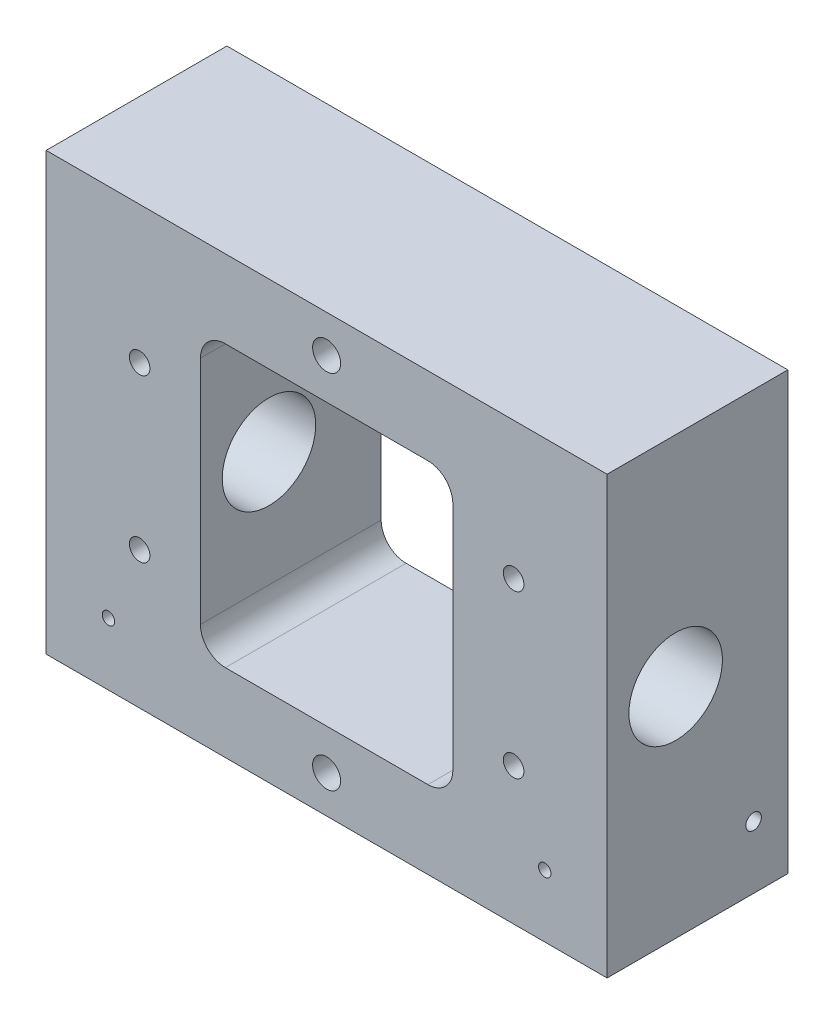
SolidWorks part; units mm, degrees
material "Lega 6061"
ref_plane "Piano frontale" through (0, 0, 0) normal (0, 0, 1) x (1, 0, 0)
ref_plane "Piano superiore" through (0, 0, 0) normal (0, 1, 0) x (1, 0, 0)
ref_plane "Piano destro" through (0, 0, 0) normal (1, 0, 0) x (0, 0, -1)
sketch "Schizzo1" plane through (0, 0, 0) normal (0, 0, 1) x (1, 0, 0)
  line L1 (0, 0) -> (90, 0)
  line L2 (0, 0) -> (0, 70)
  line L3 (0, 70) -> (90, 70)
  line L4 (90, 0) -> (90, 70)
  dimension "D1" = 90
  dimension "D2" = 70
extrude "Estrusione-Estrusione1" add sketch "Schizzo1" against normal blind 29
sketch "Schizzo2" plane through (0, 0, 0) normal (-1, 0, 0) x (0, 0, 1)
  line L0 (-29, 35) -> (0, 35) construction
  line L1 (-29, 70) -> (-29, 0) construction
  line L2 (0, 70) -> (0, 0) construction
  circle A0 centre (-11, 35) radius 7.5
  dimension "D1" = 15
  dimension "D2" = 18
extrude "Taglio-Estrusione1" cut sketch "Schizzo2" against normal through all
sketch "Schizzo3" plane through (0, 0, -29) normal (0, 0, -1) x (-1, 0, 0)
  line L0 (-94.314, 64) -> (4.9562, 64) construction
  line L2 (-90, 70) -> (0, 70) construction
  line L4 (-90, 35) -> (0, 35) construction
  line L5 (-90, 0) -> (-90, 70) construction
  line L6 (0, 70) -> (0, 0) construction
  line L7 (-94.314, 6) -> (4.9562, 6) construction
  line L8 (-45, 70) -> (-45, 0) construction
  line L9 (0, 0) -> (-90, 0) construction
  point P16 (-45, 64)
  point P17 (-45, 6)
  dimension "D1" = 6
hole_wizard "Foro lamato per Vite M4 a testa cilindrica piana-1" positions "Schizzo3D1" profile "Schizzo4" counterbore size "M4" standard "ISO" end condition through all
sketch3d "Schizzo3D1"
  point P0 (45, 64, -29)
  point P3 (45, 6, -29)
sketch "Schizzo4" plane through (45, 64, -29) normal (1, 0, 0) x (0, 1, 0)
  line L0 (0, 0) -> (0, 29)
  line L1 (0, 29) -> (2.25, 29)
  line L3 (2.25, 29) -> (2.25, 2.6)
  line L4 (2.25, 2.6) -> (4, 2.6)
  line L5 (4, 2.6) -> (4, 0)
  line L7 (4, 0) -> (0, 0)
  line L11 (0, -6.35) -> (0, 107.95) construction
  dimension "Thru Hole Dia." = 4.5
  dimension "Thru Hole Depth" = 29
  dimension "C'Bore Dia." = 8
  dimension "C'Bore Depth" = 2.6
ref_axis "Assi1" through (90, 35, -11) along (-1, 0, 0)
sketch "Schizzo14" plane through (0, 0, 0) normal (0, 0, 1) x (1, 0, 0)
  line L0 (45, 70) -> (45, 0) construction
  line L2 (61.25, 12.5) -> (28.75, 12.5)
  line L3 (65.25, 16.5) -> (65.25, 53.5)
  line L4 (90, 35) -> (0, 35) construction
  line L5 (61.25, 57.5) -> (28.75, 57.5)
  line L6 (24.75, 16.5) -> (24.75, 53.5)
  line L7 (65.25, 12.5) -> (24.75, 57.5) construction
  line L8 (65.25, 57.5) -> (24.75, 12.5) construction
  line L9 (0, 0) -> (90, 0) construction
  arc A0 (61.25, 57.5) -> (65.25, 53.5) centre (61.25, 53.5) cw
  arc A1 (65.25, 16.5) -> (61.25, 12.5) centre (61.25, 16.5) cw
  arc A2 (28.75, 12.5) -> (24.75, 16.5) centre (28.75, 16.5) cw
  arc A3 (24.75, 53.5) -> (28.75, 57.5) centre (28.75, 53.5) cw
  point P2 (45, 35)
  point P3 (45, 35)
  dimension "D1" = 4
  dimension "D2" = 45
  dimension "D3" = 40.5
  dimension "D4" = 12.5
extrude "Taglio-Estrusione4" cut sketch "Schizzo14" against normal through all
sketch "Schizzo16" plane through (0, 0, 0) normal (0, 0, 1) x (1, 0, 0)
  line L0 (45, 70) -> (45, 0) construction
  line L1 (0, 35) -> (90, 35) construction
  line L2 (0, 70) -> (0, 0) construction
  line L3 (0, 0) -> (90, 0) construction
  circle A0 centre (10, 10) radius 1
  circle A1 centre (80, 10) radius 1
  dimension "D1" = 2
  dimension "D2" = 10
  dimension "D3" = 10
  dimension "D4" = 35
  dimension "D5" = 25
extrude "Taglio-Estrusione6" cut sketch "Schizzo16" against normal through all
sketch "Schizzo17" plane through (0, 0, -29) normal (0, 0, -1) x (-1, 0, 0)
  line L0 (-45, 70) -> (-45, 0.5122) construction
  line L1 (-90, 70) -> (0, 70) construction
  line L2 (-45, 70) -> (-45, 0) construction
  line L3 (0, 35) -> (-90, 35) construction
  circle A0 centre (-10, 10) radius 8
  circle A1 centre (-80, 10) radius 8
  dimension "D1" = 16
extrude "Taglio-Estrusione8" cut sketch "Schizzo17" against normal blind 13
sketch "Schizzo18" plane through (0, 0, 0) normal (0, 0, 1) x (1, 0, 0)
  line L0 (0, 70) -> (90, 0) construction
  line L1 (90, 70) -> (0, 0) construction
  line L2 (45, 35) -> (45, 70) construction
  line L3 (15, 35.0996) -> (15, 74.2174) construction
  line L4 (24.75, 35) -> (0, 35) construction
  line L5 (24.75, 53.5) -> (24.75, 16.5) construction
  line L6 (90, 35) -> (0, 35) construction
  line L7 (90, 70) -> (0, 70) construction
  line L8 (45, 70) -> (45, 0) construction
  point P9 (15, 22)
  point P11 (45, 35)
  point P17 (15, 48)
  point P24 (75, 22)
  point P25 (75, 48)
  dimension "D1" = 13
  dimension "D2" = 30
hole_wizard "Foro filettato M4-1" positions "Schizzo20" profile "Schizzo19" tap size "M4" standard "ISO" end condition through all
sketch "Schizzo20" plane through (0, 0, 0) normal (0, 0, 1) x (1, 0, 0)
  point P0 (15, 48)
  point P3 (15, 22)
  point P6 (75, 48)
  point P9 (75, 22)
cosmetic thread "Filettatura del foro1" parameters "D2"=4
cosmetic thread "Filettatura del foro2" parameters "D2"=4
cosmetic thread "Filettatura del foro3" parameters "D2"=4
cosmetic thread "Filettatura del foro4" parameters "D2"=4
sketch "Schizzo19" plane through (15, 48, 0) normal (1, 0, 0) x (0, -1, 0)
  line L0 (0, 0) -> (0, 29)
  line L1 (0, 29) -> (1.65, 29)
  line L2 (1.65, 29) -> (1.65, 0)
  line L5 (1.65, 0) -> (0, 0)
  line L11 (0, -6.35) -> (0, 107.95) construction
  dimension "Thru Tap Drill Dia." = 3.3
  dimension "Thru Tap Drill Depth" = 29
sketch "Schizzo21" plane through (0, 0, -29) normal (0, 0, -1) x (-1, 0, 0)
  line L0 (-70, 73.919) -> (-70, -6.106) construction
  line L1 (-45, 70) -> (-45, 0) construction
  line L2 (-90, 70) -> (0, 0) construction
  line L3 (0, 70) -> (-90, 0) construction
  line L5 (-20, 72.5272) -> (-20, -6.106) construction
  point P6 (-70, 54.4444)
  point P9 (-70, 15.5556)
  point P14 (-20, 54.4444)
  point P15 (-20, 15.5556)
  dimension "D1" = 25
  dimension "D2" = 25
hole_wizard "Foro filettato M3-1" positions "Schizzo23" profile "Schizzo22" tap size "M3" standard "ISO"
sketch "Schizzo23" plane through (0, 0, -29) normal (0, 0, -1) x (-1, 0, 0)
  point P0 (-70, 54.4444)
  point P3 (-70, 15.5556)
  point P6 (-20, 54.4444)
  point P9 (-20, 15.5556)
sketch "Schizzo22" plane through (70, 54.4444, -29) normal (1, 0, 0) x (0, 1, 0)
  line L0 (0, 0) -> (0, 12.7511)
  line L1 (0, 12.7511) -> (1.25, 12)
  line L2 (1.25, 12) -> (1.25, 0)
  line L5 (1.25, 0) -> (0, 0)
  line L10 (0, 12.7511) -> (-1.25, 12) construction
  line L11 (0, -6.35) -> (0, 107.95) construction
  dimension "Tap Drill Dia." = 2.5
  dimension "Tap Drill Depth" = 12
  dimension "Drill Angle" = 118
cosmetic thread "Filettatura del foro5" parameters "D1"=8, "D2"=3
cosmetic thread "Filettatura del foro6" parameters "D1"=8, "D2"=3
cosmetic thread "Filettatura del foro7" parameters "D1"=8, "D2"=3
cosmetic thread "Filettatura del foro8" parameters "D1"=8, "D2"=3
sketch "Schizzo24" plane through (0, 0, 0) normal (-1, 0, 0) x (0, 0, 1)
  line L0 (-16, 18) -> (-16, 2) construction
  line L1 (-16, 10) -> (-29, 10) construction
  point P6 (-23.5, 10)
  dimension "D1" = 7.5
hole_wizard "Foro filettato M3-2" positions "Schizzo26" profile "Schizzo27" tap size "M3" standard "ISO" end condition up to next
sketch "Schizzo26" plane through (0, 0, 0) normal (-1, 0, 0) x (0, 0, 1)
  point P0 (-23.5, 10)
sketch "Schizzo27" plane through (0, 10, -23.5) normal (0, 1, 0) x (0, 0, 1)
  line L0 (0, 0) -> (0, 2)
  line L1 (0, 2) -> (1.25, 2)
  line L2 (1.25, 2) -> (1.25, 0)
  line L5 (1.25, 0) -> (0, 0)
  line L11 (0, -6.35) -> (0, 107.95) construction
  dimension "Thru Tap Drill Dia." = 2.5
  dimension "Thru Tap Drill Depth" = 2
cosmetic thread "Filettatura del foro9" parameters "D2"=3
sketch "Schizzo28" plane through (0, 0, 0) normal (0, -1, 0) x (1, 0, 0)
  line L0 (2, -16) -> (18, -16) construction
  line L1 (10, -16) -> (10, -29) construction
  line L2 (94.314, -29) -> (-4.9562, -29) construction
  point P8 (10, -23.5)
  dimension "D1" = 7.5
hole_wizard "Foro filettato M3-3" positions "Schizzo30" profile "Schizzo31" tap size "M3" standard "ISO" end condition up to next
sketch "Schizzo30" plane through (0, 0, 0) normal (0, -1, 0) x (-1, 0, 0)
  point P0 (-10, 23.5)
sketch "Schizzo31" plane through (10, 0, -23.5) normal (1, 0, 0) x (0, 0, -1)
  line L0 (0, 0) -> (0, 2)
  line L1 (0, 2) -> (1.25, 2)
  line L2 (1.25, 2) -> (1.25, 0)
  line L5 (1.25, 0) -> (0, 0)
  line L11 (0, -6.35) -> (0, 107.95) construction
  dimension "Thru Tap Drill Dia." = 2.5
  dimension "Thru Tap Drill Depth" = 2
cosmetic thread "Filettatura del foro10" parameters "D2"=3
sketch "Schizzo32" plane through (0, 0, 0) normal (0, -1, 0) x (1, 0, 0)
  line L0 (72, -16) -> (88, -16) construction
  line L1 (72, -16) -> (88, -16) construction
  line L2 (80, -16) -> (80, -29) construction
  line L3 (94.314, -29) -> (-4.9562, -29) construction
  line L5 (90, -29) -> (90, 0) construction
  point P9 (80, -23.5)
  point P12 (90, -20.2641)
  dimension "D1" = 7.5
  dimension "D2" = 5.5
  dimension "D3" = 10
hole_wizard "Foro filettato M3-4" positions "Schizzo34" profile "Schizzo35" tap size "M3" standard "ISO" end condition up to next
sketch "Schizzo34" plane through (0, 0, 0) normal (0, -1, 0) x (-1, 0, 0)
  point P0 (-80, 23.5)
sketch "Schizzo35" plane through (80, 0, -23.5) normal (1, 0, 0) x (0, 0, -1)
  line L0 (0, 0) -> (0, 2)
  line L1 (0, 2) -> (1.25, 2)
  line L2 (1.25, 2) -> (1.25, 0)
  line L5 (1.25, 0) -> (0, 0)
  line L11 (0, -6.35) -> (0, 107.95) construction
  dimension "Thru Tap Drill Dia." = 2.5
  dimension "Thru Tap Drill Depth" = 2
cosmetic thread "Filettatura del foro11" parameters "D2"=3
sketch "Schizzo36" plane through (90, 0, 0) normal (1, 0, 0) x (0, 0, -1)
  line L0 (16, 18) -> (16, 2) construction
  line L1 (16, 10) -> (29, 10) construction
  point P8 (23.5, 10)
hole_wizard "Foro filettato M3-5" positions "Schizzo38" profile "Schizzo37" tap size "M3" standard "ISO" end condition up to next
sketch "Schizzo38" plane through (90, 0, 0) normal (1, 0, 0) x (0, 0, -1)
  point P0 (23.5, 10)
cosmetic thread "Filettatura del foro12" parameters "D2"=3
sketch "Schizzo37" plane through (90, 10, -23.5) normal (0, 1, 0) x (0, 0, -1)
  line L0 (0, 0) -> (0, 2)
  line L1 (0, 2) -> (1.25, 2)
  line L2 (1.25, 2) -> (1.25, 0)
  line L5 (1.25, 0) -> (0, 0)
  line L11 (0, -6.35) -> (0, 107.95) construction
  dimension "Thru Tap Drill Dia." = 2.5
  dimension "Thru Tap Drill Depth" = 2
